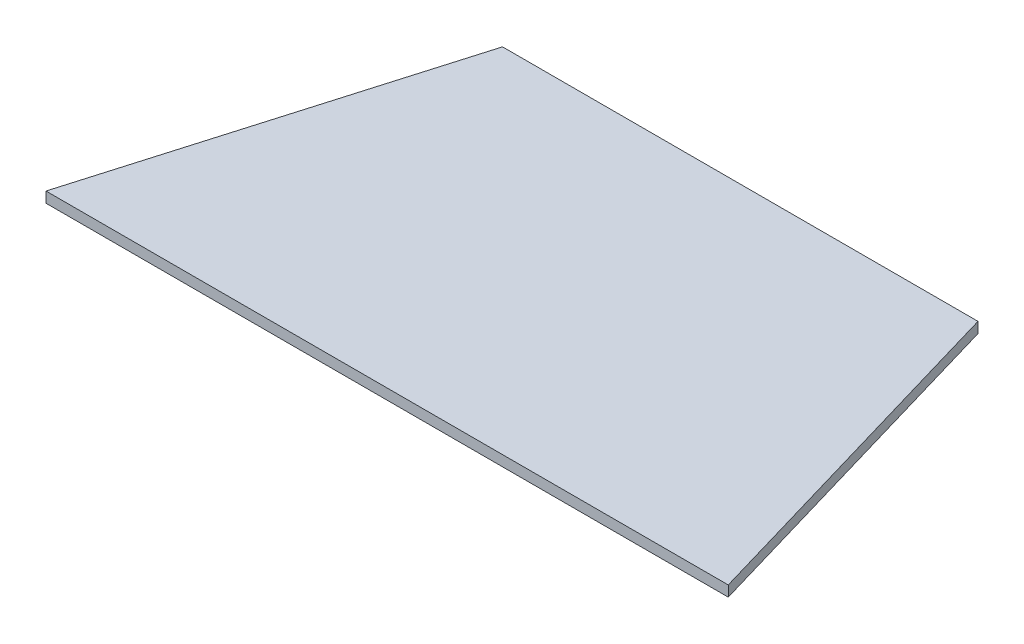
SolidWorks part; units mm, degrees
ref_plane "Front Plane" through (0, 0, 0) normal (0, 0, 1) x (1, 0, 0)
ref_plane "Top Plane" through (0, 0, 0) normal (0, 1, 0) x (1, 0, 0)
ref_plane "Right Plane" through (0, 0, 0) normal (1, 0, 0) x (0, 0, -1)
sketch "Sketch1" plane through (0, 0, 0) normal (0, 1, 0) x (1, 0, 0)
  line L0 (-13.2, 0) -> (180, 0)
  line L3 (90, 0) -> (90, 100) construction
  line L5 (-13.2, 0) -> (16.0799, 100)
  line L6 (180, 0) -> (150.7201, 100)
  line L7 (16.0799, 100) -> (150.7201, 100)
extrude "Boss-Extrude1" add sketch "Sketch1" along normal blind 3
